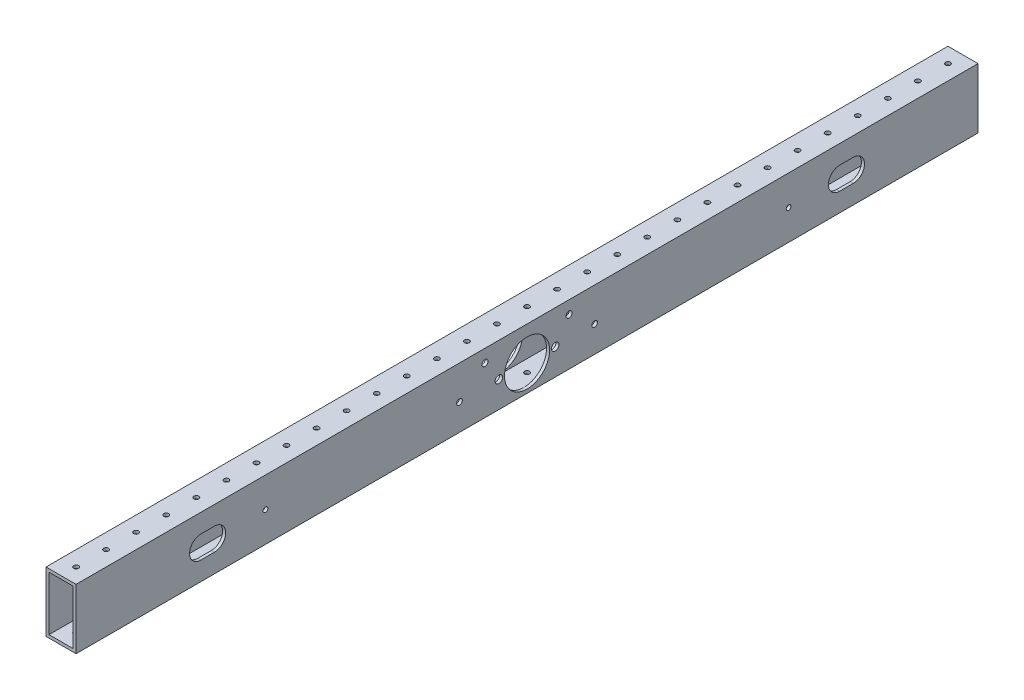
SolidWorks part; units mm, degrees
ref_plane "Front" through (0, 0, 0) normal (0, 0, 1) x (1, 0, 0)
ref_plane "Top" through (0, 0, 0) normal (0, 1, 0) x (1, 0, 0)
ref_plane "Right" through (0, 0, 0) normal (1, 0, 0) x (0, 0, -1)
sketch "Sketch1" plane through (0, 0, 0) normal (0, 0, 1) x (1, 0, 0)
  line L5 (-12.7, -25.4) -> (12.7, -25.4)
  line L6 (-12.7, -25.4) -> (-12.7, 25.4)
  line L7 (-12.7, 25.4) -> (12.7, 25.4)
  line L8 (12.7, -25.4) -> (12.7, 25.4)
  line L9 (-12.7, -25.4) -> (12.7, 25.4) construction
  line L10 (-12.7, 25.4) -> (12.7, -25.4) construction
  point P0 (0, 0)
  dimension "D1" = 50.8
  dimension "D2" = 25.4
extrude "Extrude-Thin1" add sketch "Sketch1" along normal mid plane 762 thin thin type one direction reverse wall 2.54
sketch "Sketch2" plane through (0, 25.4, 0) normal (0, 1, 0) x (1, 0, 0)
  line L0 (0, -381) -> (0, -368.3) construction
  line L1 (12.7, -381) -> (-12.7, -381) construction
  circle A0 centre (0, -368.3) radius 2.0701
  dimension "D1" = 4.1402
  dimension "D2" = 12.7
extrude "Cut-Extrude1" cut sketch "Sketch2" against normal through all
pattern_linear "LPattern1" count 31 spacing 25.4 along (0, 0, -1) of "Cut-Extrude1"
sketch "Sketch3" plane through (12.7, 0, 0) normal (1, 0, 0) x (0, 0, -1)
  line L0 (-381, 0) -> (381, 0) construction
  line L1 (-381, -25.4) -> (-381, 25.4) construction
  line L2 (381, -25.4) -> (381, 25.4) construction
  line L3 (0, -3.175) -> (-266.6811, 0) construction
  line L4 (0, 25.4) -> (0, -25.4) construction
  line L5 (-381, 25.4) -> (381, 25.4) construction
  line L6 (-381, -25.4) -> (381, -25.4) construction
  line L7 (-275.5711, 0) -> (-264.1411, 0) construction
  line L10 (-57.0865, -3.175) -> (57.0865, -3.175) construction
  line L11 (35.4965, 14.605) -> (-35.4965, 14.605) construction
  line L12 (-259.3488, 0) -> (-263.0149, 6.35) construction
  line L13 (-263.0149, 6.35) -> (-270.3473, 6.35) construction
  line L14 (-270.3473, 6.35) -> (-274.0134, 0) construction
  line L15 (-274.0134, 0) -> (-270.3473, -6.35) construction
  line L16 (-270.3473, -6.35) -> (-263.0149, -6.35) construction
  line L17 (-263.0149, -6.35) -> (-259.3488, 0) construction
  line L18 (-275.5711, 9.525) -> (-264.1411, 9.525)
  line L19 (-275.5711, -9.525) -> (-264.1411, -9.525)
  circle A0 centre (-266.6811, 0) radius 101.6 construction
  circle A2 centre (0, -3.175) radius 101.6 construction
  circle A4 centre (0, -3.175) radius 19.05
  circle A8 centre (-23.8125, -3.175) radius 3.175
  circle A9 centre (23.8125, -3.175) radius 3.175
  circle A10 centre (-57.0865, -3.175) radius 2.413
  circle A11 centre (57.0865, -3.175) radius 2.413
  circle A12 centre (-35.4965, 14.605) radius 2.54
  circle A13 centre (35.4965, 14.605) radius 2.54
  circle A14 centre (-266.6811, 0) radius 6.35 construction
  circle A15 centre (-266.6811, 0) radius 9.525 construction
  arc A16 (-275.5711, 9.525) -> (-275.5711, -9.525) centre (-275.5711, 0) ccw
  arc A17 (-264.1411, -9.525) -> (-264.1411, 9.525) centre (-264.1411, 0) ccw
  circle A18 centre (-220.9611, 0) radius 2.0193
  point P9 (0, 0)
  point P29 (-269.8561, 0)
  point P33 (0, -3.175)
  point P42 (0, 14.605)
  dimension "D1" = 203.2
  dimension "D6" = 38.1
  dimension "D7" = 6.35
  dimension "D11" = 4.826
  dimension "D14" = 5.08
  dimension "D4" = 19.05
  dimension "D5" = 12.7
  dimension "D17" = 4.0386
  dimension "D3" = 3.175
  dimension "D8" = 23.8125
  dimension "D9" = 23.8125
  dimension "D10" = 33.274
  dimension "D12" = 17.78
  dimension "D13" = 11.684
  dimension "D15" = 2.54
  dimension "D16" = 8.89
  dimension "D18" = 45.72
  dimension "D2" = 266.7
extrude "Cut-Extrude2" cut sketch "Sketch3" against normal through all contours A4 | A8 | A10 | A12 | A9 | A13 | A11 region at (12.7, -3.175, 0) region at (12.7, -3.175, 23.8125) region at (12.7, -3.175, -23.8125) region at (12.7, -3.175, 57.0865) region at (12.7, -3.175, -57.0865) region at (12.7, 14.605, 35.4965) region at (12.7, 14.605, -35.4965)
extrude "Cut-Extrude3" cut sketch "Sketch3<3>" against normal through all contours L19 A17 L18 A16 | A18 region at (12.7, 0, 269.8561) region at (12.7, 0, 220.9611)
sketch "Sketch3<3>" plane through (12.7, 0, 0) normal (1, 0, 0) x (0, 0, -1) same geometry as "Sketch3"
mirror "Mirror1" about plane through (0, 0, 0) normal (0, 0, 1) of "Cut-Extrude3"
equation "\"lenght\"= 32 - 2"
equation "\"D1@Extrude-Thin1\"=\"lenght\""
equation "\"D1@LPattern1\"=\"lenght\"+1"
equation "\"D9@Sketch3\"=\"D8@Sketch3\""
